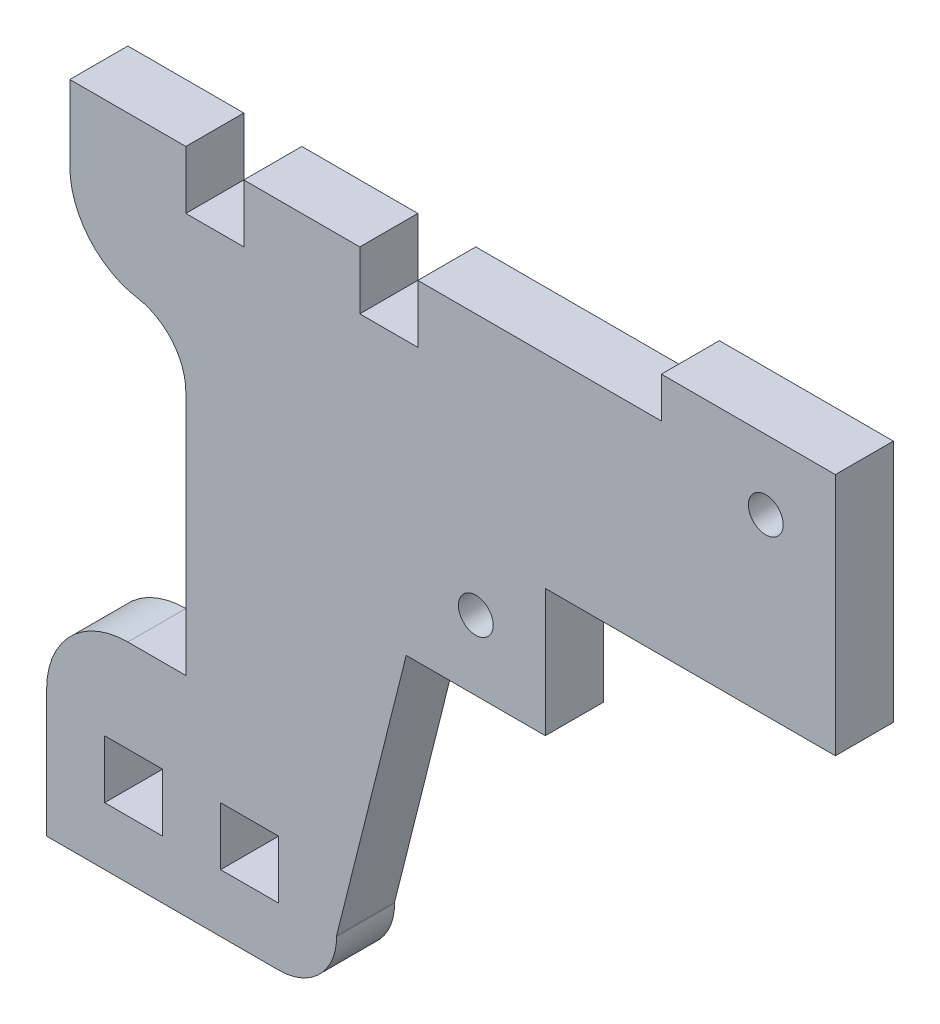
SolidWorks part; units mm, degrees
ref_plane "Plan de face" through (0, 0, 0) normal (0, 0, 1) x (1, 0, 0)
ref_plane "Plan de dessus" through (0, 0, 0) normal (0, 1, 0) x (1, 0, 0)
ref_plane "Plan de droite" through (0, 0, 0) normal (1, 0, 0) x (0, 0, -1)
sketch "Esquisse1" plane through (0, 0, 0) normal (0, 0, 1) x (1, 0, 0)
  line L0 (31, 19) -> (43, 19)
  line L1 (5, 0) -> (10, 0)
  line L2 (0, 0) -> (0, 8)
  line L3 (12, 42.5) -> (17, 42.5)
  line L4 (68, 30) -> (68, 51)
  line L5 (27, 42.5) -> (32, 42.5)
  line L6 (2, 42.5) -> (2, 47.5)
  line L7 (2, 47.5) -> (12, 47.5)
  line L8 (12, 42.5) -> (12, 47.5)
  line L9 (15, 0) -> (20, 0)
  line L10 (17, 42.5) -> (17, 47.5)
  line L11 (17, 47.5) -> (27, 47.5)
  line L12 (27, 42.5) -> (27, 47.5)
  line L13 (15, 0) -> (15, -5)
  line L14 (10, -5) -> (5, -5)
  line L15 (10, 0) -> (10, -5)
  line L16 (5, 0) -> (5, -5)
  line L18 (0, 0) -> (0, -5.81)
  line L19 (2, 34) -> (2, 42.5)
  line L20 (0, 8) -> (12, 8)
  line L22 (2, 34) -> (12, 34)
  line L23 (12, 8) -> (12, 34)
  line L24 (20, 0) -> (20, -5)
  line L25 (43, 19) -> (43, 30)
  line L26 (43, 30) -> (68, 30)
  line L27 (53, 47.5) -> (53, 51)
  line L28 (53, 51) -> (68, 51)
  line L29 (32, 42.5) -> (32, 47.5)
  line L30 (31, 19) -> (25, -4.929)
  line L31 (20, -5) -> (15, -5)
  line L32 (25, -4.929) -> (25, -10)
  line L33 (25, -10) -> (0, -10)
  line L34 (0, -5.81) -> (0, -10)
  line L35 (32, 47.5) -> (53, 47.5)
  circle A0 centre (62, 45) radius 1.5
  circle A1 centre (37, 25) radius 1.5
  circle A2 centre (37, 25) radius 1.5 construction
  circle A3 centre (62, 45) radius 1.5 construction
  dimension "D9" = 3
  dimension "D11" = 6
  dimension "D14" = 6
  dimension "D12" = 6
  dimension "D3" = 10
  dimension "D4" = 5
  dimension "D5" = 5
  dimension "D6" = 10
  dimension "D7" = 8
  dimension "D8" = 26
  dimension "D10" = 5
  dimension "D13" = 12
  dimension "D16" = 6
  dimension "D17" = 15
  dimension "D18" = 42.5
  dimension "D19" = 2
  dimension "D20" = 5
  dimension "D21" = 5
  dimension "D22" = 5
  dimension "D23" = 5
  dimension "D24" = 25
extrude "Boss.-Extru.1" add sketch "Esquisse1" along normal blind 5
fillet "Congé1" radius 7 2 edges at (0, 8, 2.5) (2, 34, 2.5)
fillet "Congé2" radius 5 1 edges at (12, 34, 2.5)
fillet "Congé3" radius 5 1 edges at (25, -10, 2.5)
